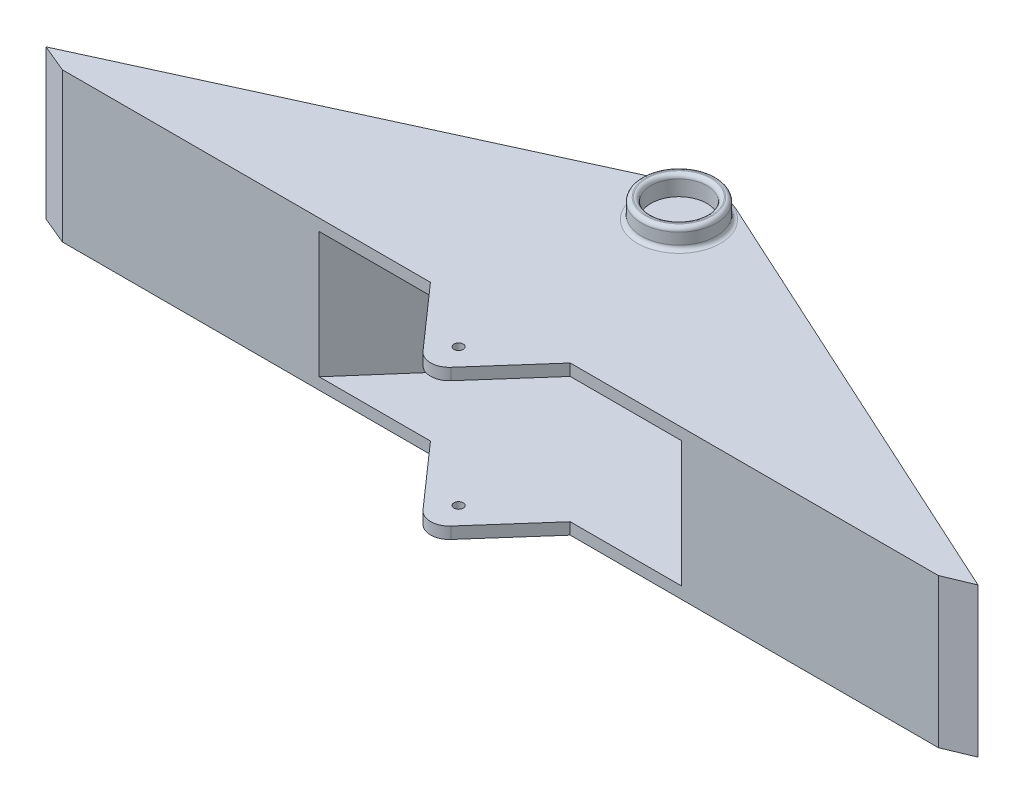
SolidWorks part; units mm, degrees
ref_plane "Front Plane" through (0, 0, 0) normal (0, 0, 1) x (1, 0, 0)
ref_plane "Top Plane" through (0, 0, 0) normal (0, 1, 0) x (1, 0, 0)
ref_plane "Right Plane" through (0, 0, 0) normal (1, 0, 0) x (0, 0, -1)
sketch "Sketch1" plane through (0, 0, 0) normal (0, 1, 0) x (1, 0, 0)
  line L0 (0, 43.0927) -> (0, -40.1782) construction
  line L1 (-54.5865, 0) -> (48.2529, 0) construction
  line L2 (-50, 0) -> (-2.083, 21.9583)
  line L3 (-0.7534, 22.0498) -> (-20, 0)
  line L4 (-20, 0) -> (-50, 0)
  line L5 (20, 0) -> (50, 0)
  line L6 (50, 0) -> (2.083, 21.9583)
  line L7 (0.7534, 22.0498) -> (20, 0)
  arc A0 (2.083, 21.9583) -> (-2.083, 21.9583) centre (0, 17.4129) ccw
  arc A1 (0.7534, 22.0498) -> (-0.7534, 22.0498) centre (0, 21.3922) ccw
  point P15 (0, 22.9129)
  dimension "D4" = 5
  dimension "D5" = 1
  dimension "D1" = 30
  dimension "D2" = 55
  dimension "D3" = 50
extrude "Boss-Extrude1" add sketch "Sketch1" along normal blind 1.25
ref_plane "Plane1" through (0, 8, 0) normal (0, 1, 0) x (1, 0, 0)
move or copy body "Body-Move/Copy1" bodies to move or copy 101 copy yes number of copies 1 translate (0, 14.75, 0)
sketch "Sketch3" plane through (0, 8, 0) normal (0, 1, 0) x (1, 0, 0)
  line L7 (19.4319, -1.25) -> (-0.1883, 21.2278)
  line L8 (50, -1.25) -> (19.4319, -1.25)
  line L9 (19.4319, -1.25) -> (0, 21.012)
  line L10 (50, -1.25) -> (19.4319, -1.25)
  line L15 (-19.4319, -1.25) -> (0.1883, 21.2278)
  line L16 (-50, -1.25) -> (-19.4319, -1.25)
  line L17 (-19.4319, -1.25) -> (0, 21.012)
  line L18 (-50, -1.25) -> (-19.4319, -1.25)
  line L29 (50, -1.25) -> (50, 0)
  line L30 (-50, -1.25) -> (-50, 0)
  line L33 (-50, 0) -> (-20, 0)
  line L34 (-20, 0) -> (-0.7534, 22.0498)
  line L35 (0.7534, 22.0498) -> (20, 0)
  line L36 (20, 0) -> (50, 0)
  line L37 (-50, 0) -> (-20, 0)
  line L38 (-20, 0) -> (-0.7534, 22.0498)
  line L39 (0.7534, 22.0498) -> (20, 0)
  line L40 (20, 0) -> (50, 0)
  arc A7 (0.7534, 22.0498) -> (-0.7534, 22.0498) centre (0, 21.3922) ccw
  arc A8 (0.7534, 22.0498) -> (-0.7534, 22.0498) centre (0, 21.3922) ccw
  dimension "D1" = 1.25
  dimension "D2" = 1.25
  dimension "D3" = 0
extrude "Boss-Extrude8" add sketch "Sketch3" along normal up to surface and the other way up to surface
chamfer "Chamfer2" distance 3 distance2 1.25 1 edges at (50, 8, 1.25)
chamfer "Chamfer3" distance 1.25 distance2 3 1 edges at (-50, 8, 1.25)
sketch "Sketch4" plane through (0, 16, 0) normal (0, 1, 0) x (1, 0, 0)
  line L0 (-19.4319, -1.25) -> (0, 21.012)
  line L1 (0, 21.012) -> (19.4319, -1.25)
  line L2 (19.4319, -1.25) -> (-19.4319, -1.25)
extrude "Boss-Extrude9" add sketch "Sketch4" against normal blind 1.25
mirror "Mirror1" about plane through (0, 8, 0) normal (0, 1, 0) of "Boss-Extrude9"
sketch "Sketch5" plane through (0, 0, 0) normal (0, -1, 0) x (1, 0, 0)
  line L0 (0, 11.4497) -> (0, -34.0912) construction
  line L1 (-7.5, 1.25) -> (7.5, 1.25)
  line L2 (47, 1.25) -> (-47, 1.25) construction
  line L3 (7.5, 1.25) -> (1.4997, 8.0504)
  line L4 (-1.4997, 8.0504) -> (-7.5, 1.25)
  arc A0 (1.4997, 8.0504) -> (-1.4997, 8.0504) centre (0, 6.7271) ccw
  point P10 (0, 9.75)
  dimension "D3" = 2
  dimension "D1" = 15
  dimension "D2" = 8.5
extrude "Boss-Extrude10" add sketch "Sketch5" against normal blind 1.25
mirror "Mirror2" about plane through (0, 8, 0) normal (0, 1, 0) of "Boss-Extrude10"
sketch "Sketch6" plane through (0, 0, 0) normal (0, -1, 0) x (-1, 0, 0)
  line L0 (0, -21.75) -> (0, 34.5468) construction
  line L1 (0, -8.7271) -> (-8.0411, -8.7271) construction
  circle A0 centre (0, -5.7271) radius 0.5
  arc A1 (-1.4997, -8.0504) -> (1.4997, -8.0504) centre (0, -6.7271) ccw construction
  dimension "D1" = 3
extrude "Cut-Extrude1" cut sketch "Sketch6" against normal up to surface (16 mm away)
sketch "Schizzo1" plane through (0, 16, 0) normal (0, 1, 0) x (1, 0, 0)
  line L0 (0, 22.4129) -> (0, -8.7271) construction
  arc A0 (2.083, 21.9583) -> (-2.083, 21.9583) centre (0, 17.4129) ccw construction
  arc A1 (-1.4997, -8.0504) -> (1.4997, -8.0504) centre (0, -6.7271) ccw construction
  circle A2 centre (0, 22.4129) radius 4.5 construction
  circle A3 centre (0, 17.9129) radius 3
  circle A4 centre (0, 17.9129) radius 4
  dimension "D1" = 6
  dimension "D2" = 8
extrude "Estrusione-Estrusione1" add sketch "Schizzo1" along normal blind 2.1
fillet "Raccordo1" radius 0.45 3 edges at (0, 18.1, -13.9129) (0, 16, -13.9129) (0, 18.1, -14.9129)
